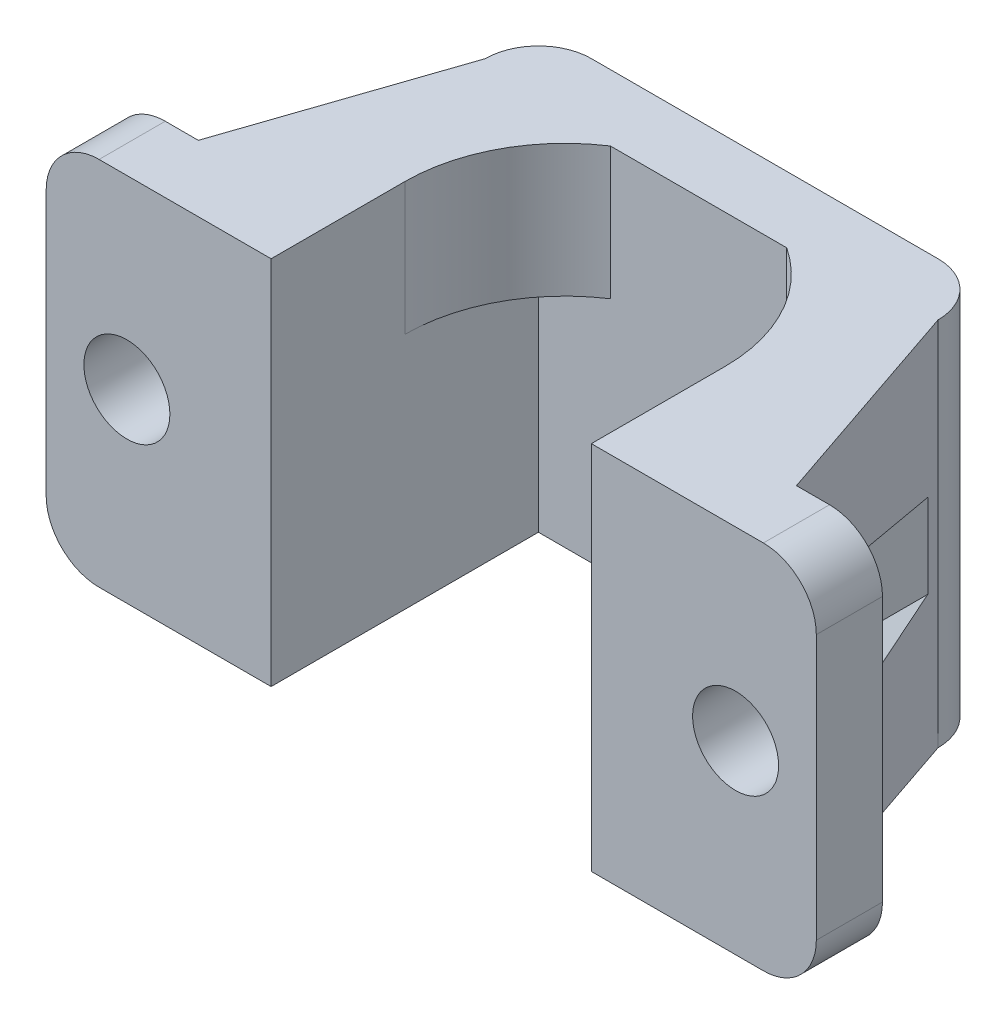
SolidWorks part; units mm, degrees
ref_plane "Alzado" through (0, 0, 0) normal (0, 0, 1) x (1, 0, 0)
ref_plane "Planta" through (0, 0, 0) normal (0, 1, 0) x (1, 0, 0)
ref_plane "Vista lateral" through (0, 0, 0) normal (1, 0, 0) x (0, 0, -1)
sketch "Croquis1" plane through (0, 0, 0) normal (0, 1, 0) x (1, 0, 0)
  line L0 (-6.05, 0) -> (-6.05, 10.1)
  line L1 (-6.05, 10.1) -> (6.05, 10.1)
  line L2 (-6.05, 0) -> (-14.55, 0)
  line L3 (-14.55, 0) -> (-14.55, 2.5)
  line L4 (-14.55, 2.5) -> (-8.55, 2.5)
  line L5 (-8.55, 2.5) -> (-8.55, 12.6)
  line L6 (-8.55, 12.6) -> (8.55, 12.6)
  line L7 (-11.3, 2.5) -> (-8.55, 10.6)
  line L8 (0, 0) -> (0, 12.6) construction
  line L9 (11.3, 2.5) -> (8.55, 10.6)
  line L10 (8.55, 2.5) -> (8.55, 12.6)
  line L11 (14.55, 2.5) -> (8.55, 2.5)
  line L12 (14.55, 0) -> (14.55, 2.5)
  line L13 (6.05, 0) -> (14.55, 0)
  line L14 (6.05, 0) -> (6.05, 10.1)
  point P16 (0, 12.6)
  point P21 (0, 10.1)
  dimension "D1" = 10.1
  dimension "D2" = 6.05
  dimension "D3" = 2.5
  dimension "D4" = 2.5
  dimension "D5" = 6
  dimension "D6" = 2.5
  dimension "D7" = 2.75
  dimension "D8" = 2
extrude "Cuerpo Base" add sketch "Croquis1" along normal blind 14 contours L1 L8 L6 L5 L4 L3 L2 L0 | L7 L4 L5 | L8 L1 L14 L13 L12 L11 L10 L6 | L11 L9 L10 region at (-7.2852, 0, -6.3102) region at (7.2852, 0, -6.3102) region at (-9.4667, 0, -5.2) region at (9.4667, 0, -5.2)
sketch "Croquis2" plane through (0, 0, 0) normal (0, 0, 1) x (1, 0, 0)
  line L0 (0, 0) -> (0, 14) construction
  line L1 (-14.55, 14) -> (-14.55, 0) construction
  circle A0 centre (-11.5, 7) radius 1.625
  circle A1 centre (11.5, 7) radius 1.625
  dimension "D2" = 3.25
  dimension "D1" = 11.5
extrude "Agujeros de sujecion" cut sketch "Croquis2" against normal blind 14
sketch "Croquis3" plane through (0, 0, 0) normal (0, 0, 1) x (1, 0, 0)
  line L1 (-14.25, 5.4123) -> (-11.5, 3.8246)
  line L2 (-11.5, 3.8246) -> (-8.75, 5.4123)
  line L3 (-8.75, 5.4123) -> (-8.75, 8.5877)
  line L4 (-8.75, 8.5877) -> (-11.5, 10.1754)
  line L5 (-11.5, 10.1754) -> (-14.25, 8.5877)
  line L6 (-14.25, 8.5877) -> (-14.25, 5.4123)
  line L7 (11.5, 3.8246) -> (14.25, 5.4123)
  line L8 (14.25, 5.4123) -> (14.25, 8.5877)
  line L9 (14.25, 8.5877) -> (11.5, 10.1754)
  line L10 (11.5, 10.1754) -> (8.75, 8.5877)
  line L11 (8.75, 8.5877) -> (8.75, 5.4123)
  line L12 (8.75, 5.4123) -> (11.5, 3.8246)
  circle A0 centre (-11.5, 7) radius 2.75 construction
  circle A1 centre (11.5, 7) radius 2.75 construction
  dimension "D1" = 5.5
  dimension "D2" = 5.5
extrude "Tuercas" cut sketch "Croquis3" against normal through all from offset 2.5 offset against normal yes
fillet "Redondeo bordes" radius 2 6 edges at (-8.55, 7, -12.6) (8.55, 7, -12.6) (14.55, 0, -1.25) (14.55, 14, -1.25) (-14.55, 0, -1.25) (-14.55, 14, -1.25)
sketch "Croquis4" plane through (0, 14, 0) normal (0, 1, 0) x (1, 0, 0)
  line L0 (-6.05, 10.1) -> (6.05, 10.1)
  line L2 (-6.05, 5.05) -> (-6.05, 10.1)
  line L3 (6.05, 10.1) -> (6.05, 5.05)
  circle A0 centre (0, 5.05) radius 6.05
  line M8 (-6.05, 0) -> (-6.05, 10.1)
  line M9 (-6.05, 10.1) -> (6.05, 10.1)
  line M10 (6.05, 10.1) -> (6.05, 0)
extrude "Saliente-Extruir2" add sketch "Croquis4" against normal blind 5 contours A0 M9 M8 | A0 M10 M9 region at (-5.2796, 14, -8.9011) region at (5.2796, 14, -8.9011)
